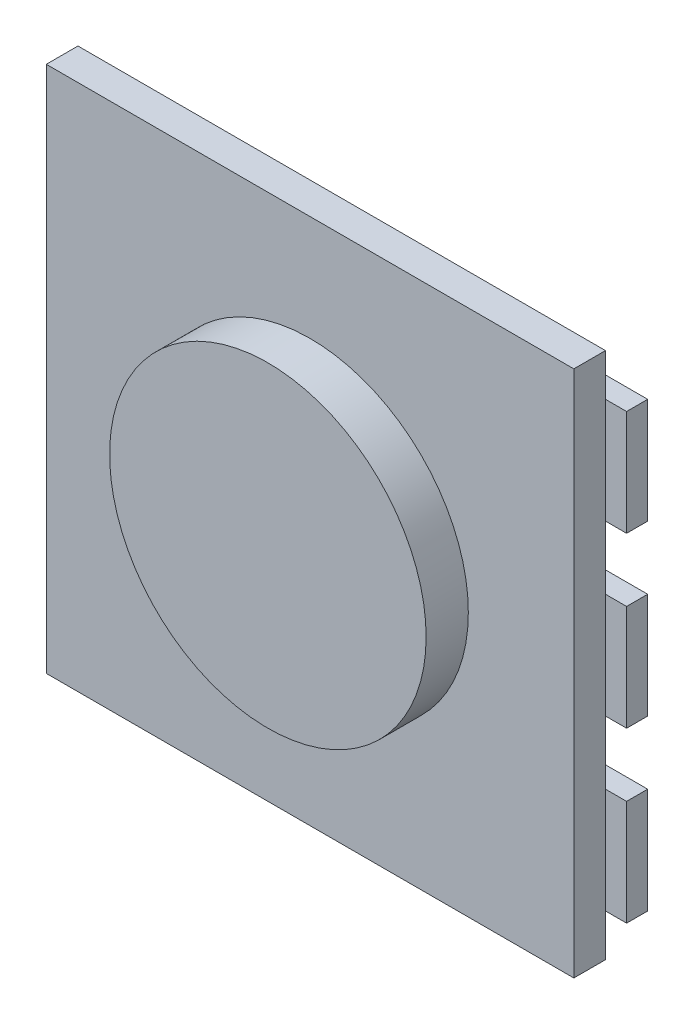
SolidWorks part; units mm, degrees
ref_plane "Plan de face" through (0, 0, 0) normal (0, 0, 1) x (1, 0, 0)
ref_plane "Plan de dessus" through (0, 0, 0) normal (0, 1, 0) x (1, 0, 0)
ref_plane "Plan de droite" through (0, 0, 0) normal (1, 0, 0) x (0, 0, -1)
sketch "Esquisse1" plane through (0, 0, 0) normal (0, 0, 1) x (1, 0, 0)
  line L0 (-14.4066, -12.1389) -> (-14.4066, -13.1389)
  line L1 (-14.2066, -10.1389) -> (-9.2066, -10.1389)
  line L2 (-14.2066, -10.1389) -> (-14.2066, -15.1389)
  line L3 (-14.2066, -15.1389) -> (-9.2066, -15.1389)
  line L4 (-9.2066, -10.1389) -> (-9.2066, -15.1389)
  line L5 (-12.0079, -10.6389) -> (-11.218, -10.6389)
  line L6 (-12.0079, -10.6389) -> (-12.0079, -11.6389)
  line L7 (-12.0079, -11.6389) -> (-11.218, -11.6389)
  line L8 (-11.218, -10.6389) -> (-11.218, -11.6389)
  line L9 (-12.1016, -13.6389) -> (-11.3117, -13.6389)
  line L10 (-12.1016, -13.6389) -> (-12.1016, -14.6389)
  line L11 (-12.1016, -14.6389) -> (-11.3117, -14.6389)
  line L12 (-11.3117, -13.6389) -> (-11.3117, -14.6389)
  line L13 (-14.4066, -10.5389) -> (-13.4066, -10.5389)
  line L14 (-14.4066, -10.5389) -> (-14.4066, -11.5389)
  line L15 (-14.4066, -11.5389) -> (-13.4066, -11.5389)
  line L16 (-13.4066, -10.5389) -> (-13.4066, -11.5389)
  line L17 (-14.4066, -13.1389) -> (-13.4066, -13.1389)
  line L18 (-13.4066, -12.1389) -> (-13.4066, -13.1389)
  line L19 (-14.4066, -12.1389) -> (-13.4066, -12.1389)
  line L20 (-14.4066, -13.7389) -> (-14.4066, -14.7389)
  line L21 (-14.4066, -14.7389) -> (-13.4066, -14.7389)
  line L22 (-13.4066, -13.7389) -> (-13.4066, -14.7389)
  line L23 (-14.4066, -13.7389) -> (-13.4066, -13.7389)
  line L24 (-10.0066, -11.5389) -> (-9.0066, -11.5389)
  line L25 (-9.0066, -13.7389) -> (-9.0066, -14.7389)
  line L26 (-10.0066, -10.5389) -> (-10.0066, -11.5389)
  line L27 (-9.0066, -12.1389) -> (-9.0066, -13.1389)
  line L28 (-10.0066, -13.7389) -> (-9.0066, -13.7389)
  line L29 (-9.0066, -10.5389) -> (-9.0066, -11.5389)
  line L30 (-10.0066, -14.7389) -> (-9.0066, -14.7389)
  line L31 (-10.0066, -13.1389) -> (-9.0066, -13.1389)
  line L32 (-10.0066, -10.5389) -> (-9.0066, -10.5389)
  line L33 (-10.0066, -13.7389) -> (-10.0066, -14.7389)
  line L34 (-10.0066, -12.1389) -> (-9.0066, -12.1389)
  line L35 (-10.0066, -12.1389) -> (-10.0066, -13.1389)
  circle A0 centre (-11.7066, -12.6389) radius 1.5
  circle A1 centre (-11.7066, -12.6389) radius 0.3949
  dimension "D3" = 3
  dimension "D1" = 5
  dimension "D2" = 5
  dimension "D4" = 2.5
  dimension "D5" = 2.5
  dimension "D6" = 1
  dimension "D7" = 0.5
  dimension "D8" = 0.5
  dimension "D9" = 1
  dimension "D10" = 1
  dimension "D11" = 0.4
  dimension "D12" = 0.2
extrude "Boss.-Extru.2" add sketch "Esquisse1" along normal blind 0.3 contours L1 L4 L3 L2
extrude "Boss.-Extru.3" add sketch "Esquisse1<5>" along normal blind 0.7 contours A0
sketch "Esquisse1<5>" plane through (0, 0, 0) normal (0, 0, 1) x (1, 0, 0) same geometry as "Esquisse1"
extrude "Boss.-Extru.4" add sketch "Esquisse1<6>" against normal blind 0.1 contours A1 region at (-11.7066, -12.6389, 0)
sketch "Esquisse1<6>" plane through (0, 0, 0) normal (0, 0, 1) x (1, 0, 0) same geometry as "Esquisse1"
extrude "Boss.-Extru.5" add sketch "Esquisse1<7>" against normal blind 0.2 contours L32 L26 L24 L4 | A0 L8 L5 L6 | L8 A0 L6 L7 | L16 L13 L2 L15 | L32 L4 L24 L29 | L34 L35 L31 L4 | L34 L4 L31 L27 | L28 L33 L30 L4 | A0 L10 L11 L12 | L10 A0 L12 L9 | L23 L2 L21 L22 | L23 L20 L21 L2 | L19 L2 L17 L18 | L19 L0 L17 L2 | L14 L15 L16 L13 | L25 L30 L33 L28 region at (-14.3066, -12.6389, 0) region at (-13.8066, -12.6389, 0) region at (-13.8066, -11.0389, 0) region at (-13.8066, -14.2389, 0) region at (-14.3066, -14.2389, 0) region at (-9.1066, -11.0389, 0) region at (-9.6066, -11.0389, 0) region at (-9.6066, -14.2389, 0) region at (-9.1066, -12.6389, 0) region at (-9.6066, -12.6389, 0) region at (-11.6066, -10.8997, 0) region at (-11.6199, -11.3987, 0) region at (-11.7066, -14.3799, 0) region at (-11.7066, -13.8804, 0)
sketch "Esquisse1<7>" plane through (0, 0, 0) normal (0, 0, 1) x (1, 0, 0) same geometry as "Esquisse1"
